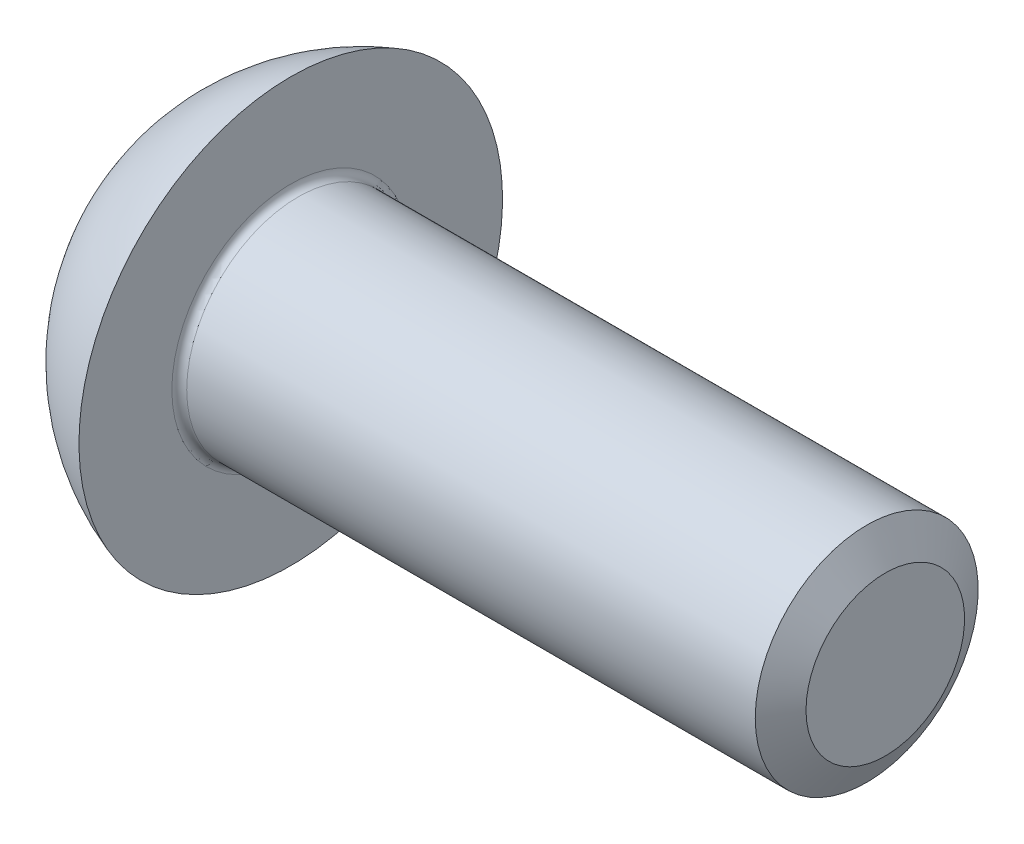
SolidWorks part; units mm, degrees
ref_plane "前视基准面" through (0, 0, 0) normal (0, 0, 1) x (1, 0, 0)
ref_plane "上视基准面" through (0, 0, 0) normal (0, 1, 0) x (1, 0, 0)
ref_plane "右视基准面" through (0, 0, 0) normal (1, 0, 0) x (0, 0, -1)
sketch "尺寸草图" plane through (0, 0, 0) normal (0, 0, 1) x (1, 0, 0)
  line L0 (0, 0) -> (8, 0) construction
  line L1 (8, 0) -> (8, 1.5) construction
  line L2 (8, 1.5) -> (7.5, 1.5) construction
  line L3 (0, 0) -> (0, 2.85) construction
  point P3 (1, 0)
  point P6 (8, 1.8)
  point P7 (0, 0.55)
  point P9 (1.65, 0)
  point P10 (1.75, 0)
  point P11 (8, 1)
  point P12 (2.79, 0)
  point P13 (2.99, 0)
  point P14 (8, 9.8)
  dimension "l" = 8
  dimension "d" = 3
  dimension "P" = 0.5
  dimension "a" = 1
  dimension "da" = 3.6
  dimension "dk" = 5.7
  dimension "e" = 2.3
  dimension "K" = 1.65
  dimension "r" = 0.1
  dimension "s" = 2
  dimension "t" = 1.04
  dimension "w" = 0.2
  dimension "zslwx" = 8
sketch "草图1" plane through (0, 0, 0) normal (0, 0, 1) x (1, 0, 0)
  line L0 (-9.65, 0) -> (0, 0) construction
  line L1 (0, 1.5) -> (-7.9, 1.5)
  line L2 (-8, 1.6) -> (-8, 2.85)
  line L3 (-9.65, 0) -> (-9.65, 1.5)
  line L4 (0, 1.5) -> (0, 0)
  line L5 (-9.65, 0) -> (0, 0)
  arc A0 (-8, 2.85) -> (-9.65, 1.5) centre (-7.0455, 0) ccw
  arc A1 (-7.9, 1.5) -> (-8, 1.6) centre (-7.9, 1.6) cw
  point P10 (-8, 1.5)
  dimension "r" = 0.1
  dimension "d" = 3
  dimension "dk" = 5.7
  dimension "k" = 1.65
  dimension "l" = 8
revolve "旋转1" add sketch "草图1" angle 360 about L0
cosmetic thread "装饰螺纹线1" parameters "D1"=8, "D2"=2.58
sketch "草图2" plane through (-9.65, 0, 0) normal (-1, 0, 0) x (0, 0, 1)
  line L1 (0, 1.1547) -> (-1, 0.5774)
  line L2 (-1, 0.5774) -> (-1, -0.5774)
  line L3 (-1, -0.5774) -> (0, -1.1547)
  line L4 (0, -1.1547) -> (1, -0.5774)
  line L5 (1, -0.5774) -> (1, 0.5774)
  line L6 (1, 0.5774) -> (0, 1.1547)
  circle A0 centre (0, 0) radius 1 construction
  dimension "s" = 2
extrude "切除-拉伸1" cut sketch "草图2" against normal blind 1.65
sketch "草图6" plane through (0, 0, 0) normal (0, 0, 1) x (1, 0, 0)
  line L0 (-8.61, 1.1547) -> (-8, 0)
  line L1 (-7.7, 1.1547) -> (-7.7, 0)
  line L2 (-7.7, 1.1547) -> (-8.61, 1.1547)
  line L3 (-9.65, 0) -> (-8, 0) construction
  line L4 (-7.7, 0) -> (-8, 0)
  line L5 (-9.65, 0) -> (-11.95, 0) construction
  dimension "t" = 1.04
  dimension "e-s" = 0.3
  dimension "k" = 1.65
  dimension "e" = 2.3
revolve "旋转2" add sketch "草图6" angle 360 about L3
sketch "草图7" plane through (0, 0, 0) normal (0, 0, 1) x (1, 0, 0)
  line L3 (-9.65, 1.1547) -> (-9.35, 0)
  line L4 (-9.65, 0) -> (-9.35, 0) construction
  line L7 (-9.65, 1.1547) -> (-9.65, 0)
  line L8 (-9.65, 0) -> (-9.35, 0)
  dimension "e-s" = 0.3
revolve "切除-旋转5" cut sketch "草图7" angle 360 about L4
sketch "草图4" plane through (0, 0, 0) normal (0, 0, 1) x (1, 0, 0)
  line L0 (-0.25, 1.5) -> (0, 1.067)
  line L1 (-0.25, 1.5) -> (0.25, 1.5)
  line L2 (0.25, 1.5) -> (0, 1.067)
  line L4 (0, -1.5) -> (0, 1.5) construction
  line L5 (-0.25, 0) -> (0.25, 0) construction
  dimension "d" = 1.5
  dimension "p" = 0.5
revolve "切除-旋转1" cut sketch "草图4" angle 360 about L5
ref_axis "基准轴1" through (-8.1887, 0, 0) along (1, 0, 0)
pattern_linear "阵列(线性)1" [suppressed] count 14 spacing 0.5 along (-1, 0, 0) of bodies 104
